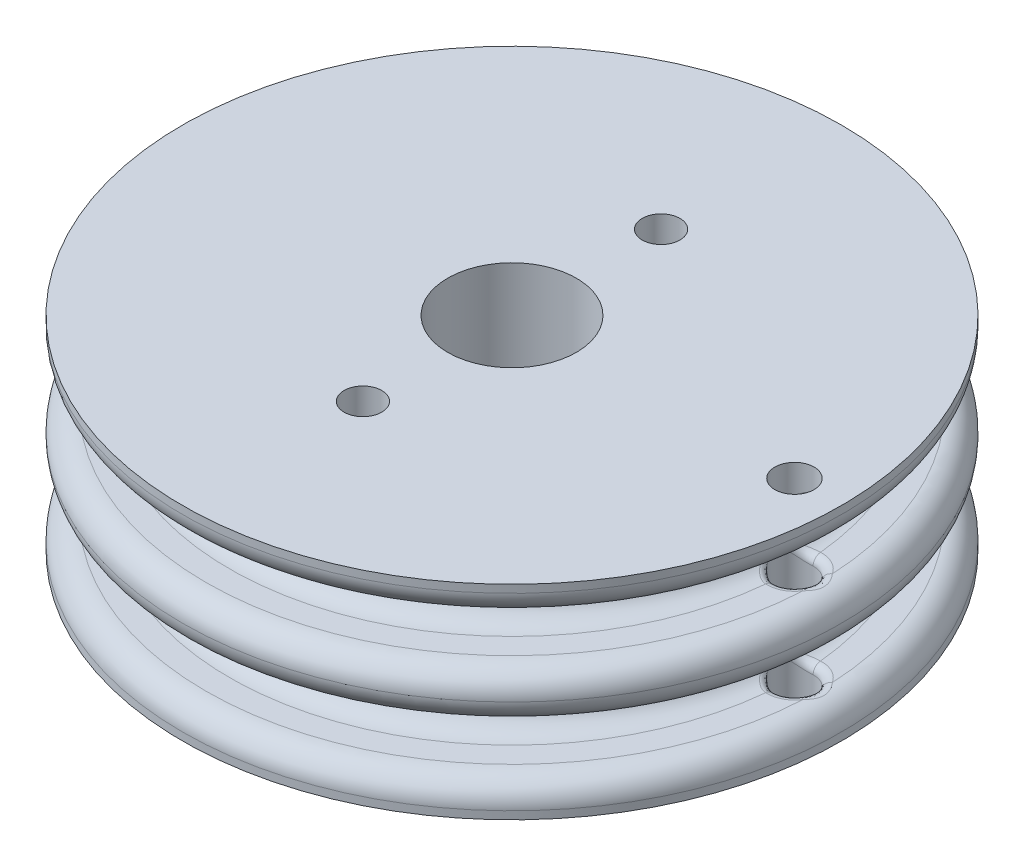
SolidWorks part; units mm, degrees
ref_plane "Plan de face" through (0, 0, 0) normal (0, 0, 1) x (1, 0, 0)
ref_plane "Plan de dessus" through (0, 0, 0) normal (0, 1, 0) x (1, 0, 0)
ref_plane "Plan de droite" through (0, 0, 0) normal (1, 0, 0) x (0, 0, -1)
sketch "Esquisse1" plane through (0, 0, 0) normal (0, 0, 1) x (1, 0, 0)
  line L0 (0, 0) -> (0, 13)
  line L1 (0, 13) -> (21, 13)
  line L2 (21, 13) -> (21, 11)
  line L3 (21, 11) -> (18, 11)
  line L4 (18, 8) -> (21, 8)
  line L5 (21, 8) -> (21, 5)
  line L6 (21, 5) -> (18, 5)
  line L7 (18, 2) -> (21, 2)
  line L8 (21, 2) -> (21, 0)
  line L9 (21, 0) -> (0, 0)
  line L10 (0, 13) -> (0, 26) construction
  arc A0 (18, 11) -> (18, 8) centre (18, 9.5) ccw
  arc A1 (18, 5) -> (18, 2) centre (18, 3.5) ccw
  dimension "D1" = 3
  dimension "D5" = 36
  dimension "D2" = 3
  dimension "D3" = 2
  dimension "D4" = 3
  dimension "D6" = 42
revolve "Révolution1" add sketch "Esquisse1" angle 360 about L10
fillet "Congé1" radius 1.5 4 edges at (0, 2, -21) (0, 5, -21) (0, 8, -21) (0, 11, -21)
sketch "Esquisse2" plane through (0, 13, 0) normal (0, 1, 0) x (1, 0, 0)
  line L0 (0, -9.5) -> (0, 9.5) construction
  circle A0 centre (18, 0) radius 1.25
  circle A1 centre (0, -9.5) radius 1.2
  circle A2 centre (0, 0) radius 4.1
  circle A3 centre (0, 0) radius 18 construction
  circle A4 centre (0, 9.5) radius 1.2
  dimension "D1" = 2.5
  dimension "D2" = 2.4
  dimension "D3" = 8.2
  dimension "D4" = 19
extrude "Enlèv. mat.-Extru.1" cut sketch "Esquisse2" against normal through all
fillet "Congé3" radius 0.5 8 edges at (19.25, 5, 0) (19.25, 2, 0) (19.25, 11, 0) (19.25, 8, 0) (16.7508, 4.3305, -0.0452) (16.7508, 2.6695, 0.0452) (16.7508, 10.3305, -0.0452) (16.7508, 8.6695, 0.0452)
